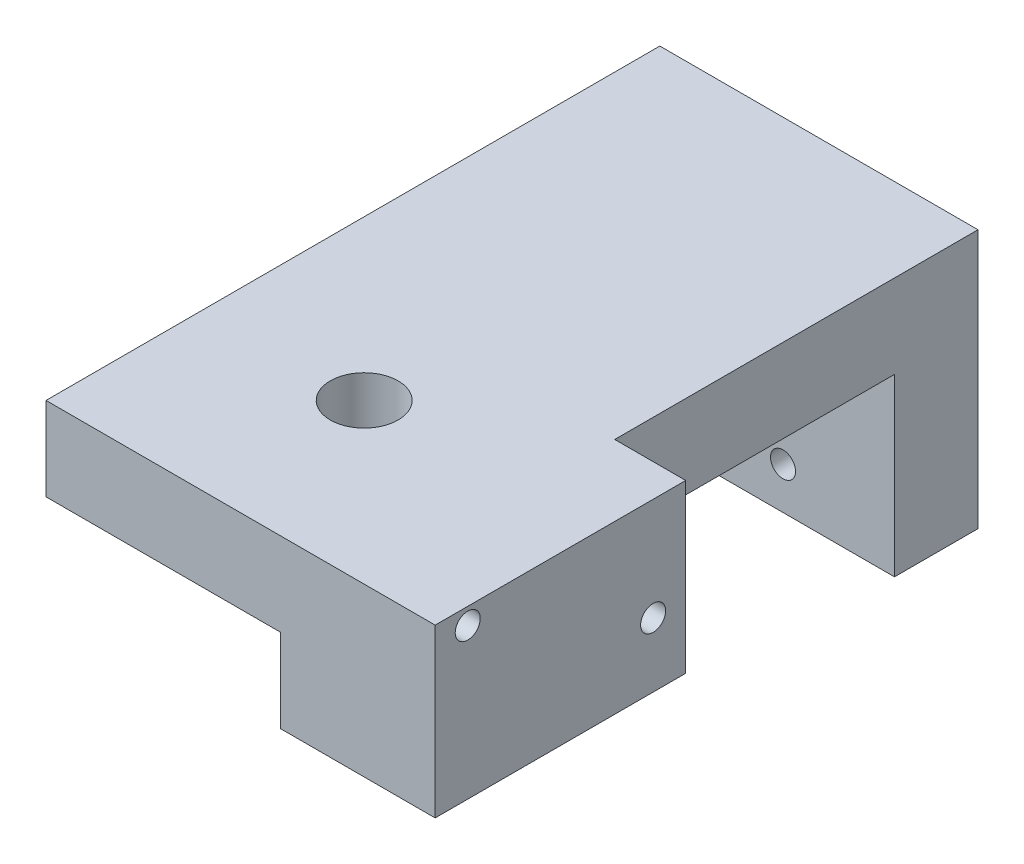
SolidWorks part; units mm, degrees
ref_plane "Front Plane" through (0, 0, 0) normal (0, 0, 1) x (1, 0, 0)
ref_plane "Top Plane" through (0, 0, 0) normal (0, 1, 0) x (1, 0, 0)
ref_plane "Right Plane" through (0, 0, 0) normal (1, 0, 0) x (0, 0, -1)
sketch "Sketch1" plane through (0, 0, 0) normal (0, 1, 0) x (1, 0, 0)
  line L1 (0, 0) -> (38.1, 0)
  line L2 (0, 0) -> (0, -63.5)
  line L3 (0, -63.5) -> (38.1, -63.5)
  line L4 (38.1, 0) -> (38.1, -63.5)
  circle A0 centre (19.05, -44.45) radius 4.064
  dimension "D2" = 8.128
  dimension "D1" = 38.1
  dimension "D3" = 19.05
  dimension "D4" = 19.05
  dimension "D5" = 63.5
extrude "Boss-Extrude1" add sketch "Sketch1" along normal blind 10
sketch "Sketch2" plane through (0, 0, 0) normal (1, 0, 0) x (0, 0, -1)
  line L1 (-63.5, 0) -> (0, 0) construction
  line L2 (-33.5, 0) -> (-33.5, -10)
  line L3 (-33.5, -10) -> (-63.5, -10)
  line L4 (-63.5, -10) -> (-63.5, 0)
  line L5 (-63.5, 10) -> (0, 10) construction
  line L6 (-63.5, 0) -> (-63.5, 10)
  line L7 (-63.5, 10) -> (-33.5, 10)
  line L8 (-33.5, 10) -> (-33.5, 0)
  circle A0 centre (-59.6, 8) radius 1.5
  circle A1 centre (-37.4, -2.3) radius 1.5
  dimension "D3" = 3
  dimension "D2" = 30
  dimension "D4" = 10.3
  dimension "D5" = 22.2
  dimension "D6" = 3.9
  dimension "D1" = 2
  dimension "D7" = 20
extrude "Boss-Extrude2" add sketch "Sketch2" along normal blind 8.5 and the other way blind 10 from surface starting at face at (38.1, 5, 31.75)
sketch "Sketch3" plane through (0, 0, 0) normal (0, 0, 1) x (1, 0, 0)
  line L0 (13.25, -3) -> (16.25, -3)
  line L1 (0, 10) -> (38.1, 10)
  line L2 (0, 10) -> (0, -21)
  line L3 (0, -21) -> (38.1, -21)
  line L4 (38.1, 10) -> (38.1, -21)
  line L6 (38.1, 10) -> (38.1, 0) construction
  line L7 (0, 10) -> (46.6, 10) construction
  line L8 (13.25, -21) -> (13.25, -3)
  line L14 (16.25, -3) -> (16.25, -21)
  circle A0 centre (4.75, 4) radius 1.5
  circle A1 centre (24.75, 4) radius 1.5
  circle A2 centre (24.75, -16) radius 1.5
  circle A3 centre (4.75, -16) radius 1.5
  dimension "D6" = 3
  dimension "D1" = 20
  dimension "D2" = 20
  dimension "D3" = 5
  dimension "D4" = 4.75
  dimension "D5" = 6
  dimension "D7" = 3
  dimension "D8" = 18
  dimension "D9" = 8.5
  dimension "D10" = 8.5
extrude "Boss-Extrude3" add sketch "Sketch3" against normal blind 10 contours L14 L3 L4 L1 L2 L8 A3 A2 A1 A0 region at (19.372, -5.1677, 0)
extrude "Cut-Extrude1" cut sketch "Sketch2<2>" along normal blind 10 contours A0 region at (0, 8, 59.6)
sketch "Sketch2<2>" plane through (0, 0, 0) normal (1, 0, 0) x (0, 0, -1) same geometry as "Sketch2"
extrude "Cut-Extrude2" cut sketch "Sketch3<2>" along normal blind 10 contours A1 | A0 region at (4.75, 4, 0) region at (24.75, 4, 0)
sketch "Sketch3<2>" plane through (0, 0, 0) normal (0, 0, 1) x (1, 0, 0) same geometry as "Sketch3"
equation "\"D6@Sketch2\"=(\"D2@Sketch2\"-\"D5@Sketch2\")/2"
